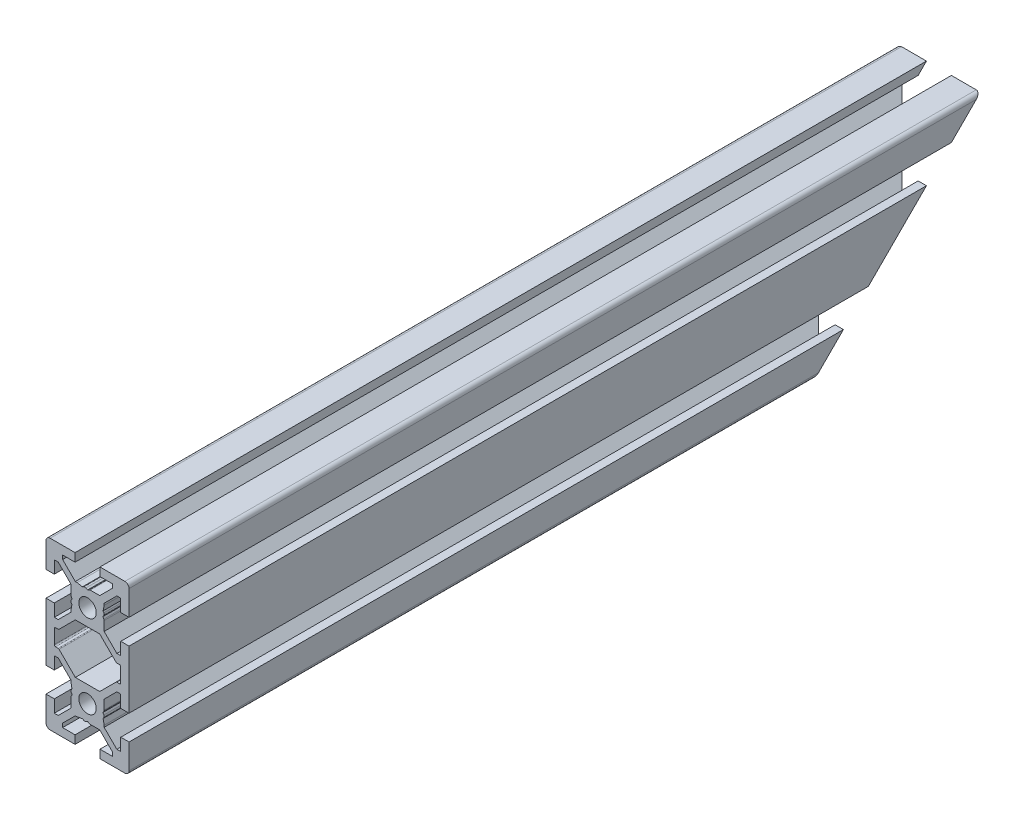
SolidWorks part; units mm, degrees
ref_plane "Front Plane" through (0, 0, 0) normal (0, 0, 1) x (1, 0, 0)
ref_plane "Top Plane" through (0, 0, 0) normal (0, 1, 0) x (1, 0, 0)
ref_plane "Right Plane" through (0, 0, 0) normal (1, 0, 0) x (0, 0, -1)
ref_plane "Plane1" through (0, 0, -600) normal (0, 0, -1) x (-1, 0, 0)
sketch "Sketch1" plane through (0, 0, -600) normal (0, 0, -1) x (-1, 0, 0)
  line L0 (8, 1.7) -> (8, -1.7)
  line L1 (7.7, -2) -> (7.0636, -2)
  line L2 (6.8515, -2.0879) -> (2.9393, -6)
  line L3 (2.9393, -6) -> (-2.9393, -6)
  line L4 (-2.9393, -6) -> (-6.8515, -2.0879)
  line L5 (-7.0636, -2) -> (-7.7, -2)
  line L6 (-8, -1.7) -> (-8, 1.7)
  line L7 (-7.7, 2) -> (-7.0636, 2)
  line L8 (-6.8515, 2.0879) -> (-2.9393, 6)
  line L9 (-2.9393, 6) -> (2.9393, 6)
  line L10 (2.9393, 6) -> (6.8515, 2.0879)
  line L11 (7.0636, 2) -> (7.7, 2)
  line L12 (10, -7) -> (10, 7)
  line L13 (10, 7) -> (8, 7)
  line L14 (8, 7) -> (8, 4)
  line L15 (8, 4) -> (7.0607, 4)
  line L16 (7.0607, 4) -> (4, 7.0607)
  line L17 (4, 7.0607) -> (4, 7.5)
  line L18 (4, 7.5) -> (3.751, 8.7811)
  line L19 (3.751, 8.7811) -> (3.933, 9.0964)
  line L20 (3.933, 9.5964) -> (3.7, 10)
  line L21 (3.7, 10) -> (3.933, 10.4036)
  line L22 (4, 10.6536) -> (4, 12.9393)
  line L23 (4, 12.9393) -> (7.0607, 16)
  line L24 (7.0607, 16) -> (8, 16)
  line L25 (8, 16) -> (8, 13)
  line L26 (8, 13) -> (10, 13)
  line L27 (10, 13) -> (10, 19)
  line L28 (9, 20) -> (3, 20)
  line L29 (3, 20) -> (3, 18)
  line L30 (3, 18) -> (6, 18)
  line L31 (6, 18) -> (6, 17.0607)
  line L32 (6, 17.0607) -> (2.9393, 14)
  line L33 (2.9393, 14) -> (2.5, 14)
  line L34 (2.5, 14) -> (1.2189, 13.751)
  line L35 (1.2189, 13.751) -> (0.9036, 13.933)
  line L36 (0.4036, 13.933) -> (0, 13.7)
  line L37 (0, 13.7) -> (-0.4036, 13.933)
  line L38 (-0.6536, 14) -> (-2.9393, 14)
  line L39 (-2.9393, 14) -> (-6, 17.0607)
  line L40 (-6, 17.0607) -> (-6, 18)
  line L41 (-6, 18) -> (-3, 18)
  line L42 (-3, 18) -> (-3, 20)
  line L43 (-3, 20) -> (-9, 20)
  line L44 (-10, 19) -> (-10, 13)
  line L45 (-10, 13) -> (-8, 13)
  line L46 (-8, 13) -> (-8, 16)
  line L47 (-8, 16) -> (-7.0607, 16)
  line L48 (-7.0607, 16) -> (-4, 12.9393)
  line L49 (-4, 12.9393) -> (-4, 12.5)
  line L50 (-4, 12.5) -> (-3.751, 11.2189)
  line L51 (-3.751, 11.2189) -> (-3.933, 10.9036)
  line L52 (-3.933, 10.4036) -> (-3.7, 10)
  line L53 (-3.7, 10) -> (-3.933, 9.5964)
  line L54 (-4, 9.3464) -> (-4, 7.0607)
  line L55 (-4, 7.0607) -> (-7.0607, 4)
  line L56 (-7.0607, 4) -> (-8, 4)
  line L57 (-8, 4) -> (-8, 7)
  line L58 (-8, 7) -> (-10, 7)
  line L59 (-10, 7) -> (-10, -7)
  line L60 (-10, -7) -> (-8, -7)
  line L61 (-8, -7) -> (-8, -4)
  line L62 (-8, -4) -> (-7.0607, -4)
  line L63 (-7.0607, -4) -> (-4, -7.0607)
  line L64 (-4, -7.0607) -> (-4, -9.3464)
  line L65 (-3.933, -9.5964) -> (-3.7, -10)
  line L66 (-3.7, -10) -> (-3.933, -10.4036)
  line L67 (-3.933, -10.9036) -> (-3.751, -11.2189)
  line L68 (-3.751, -11.2189) -> (-4, -12.5)
  line L69 (-4, -12.5) -> (-4, -12.9393)
  line L70 (-4, -12.9393) -> (-7.0607, -16)
  line L71 (-7.0607, -16) -> (-8, -16)
  line L72 (-8, -16) -> (-8, -13)
  line L73 (-8, -13) -> (-10, -13)
  line L74 (-10, -13) -> (-10, -19)
  line L75 (-9, -20) -> (-3, -20)
  line L76 (-3, -20) -> (-3, -18)
  line L77 (-3, -18) -> (-6, -18)
  line L78 (-6, -18) -> (-6, -17.0607)
  line L79 (-6, -17.0607) -> (-2.9393, -14)
  line L80 (-2.9393, -14) -> (-0.6536, -14)
  line L81 (-0.4036, -13.933) -> (0, -13.7)
  line L82 (0, -13.7) -> (0.4036, -13.933)
  line L83 (0.9036, -13.933) -> (1.2189, -13.751)
  line L84 (1.2189, -13.751) -> (2.5, -14)
  line L85 (2.5, -14) -> (2.9393, -14)
  line L86 (2.9393, -14) -> (6, -17.0607)
  line L87 (6, -17.0607) -> (6, -18)
  line L88 (6, -18) -> (3, -18)
  line L89 (3, -18) -> (3, -20)
  line L90 (3, -20) -> (9, -20)
  line L91 (10, -19) -> (10, -13)
  line L92 (10, -13) -> (8, -13)
  line L93 (8, -13) -> (8, -16)
  line L94 (8, -16) -> (7.0607, -16)
  line L95 (7.0607, -16) -> (4, -12.9393)
  line L96 (4, -12.9393) -> (4, -10.6536)
  line L97 (3.933, -10.4036) -> (3.7, -10)
  line L98 (3.7, -10) -> (3.933, -9.5964)
  line L99 (3.933, -9.0964) -> (3.751, -8.7811)
  line L100 (3.751, -8.7811) -> (4, -7.5)
  line L101 (4, -7.5) -> (4, -7.0607)
  line L102 (4, -7.0607) -> (7.0607, -4)
  line L103 (7.0607, -4) -> (8, -4)
  line L104 (8, -4) -> (8, -7)
  line L105 (8, -7) -> (10, -7)
  circle A0 centre (0, -10) radius 2.1
  circle A1 centre (0, 10) radius 2.1
  arc A2 (7.7, 2) -> (8, 1.7) centre (7.7, 1.7) cw
  arc A3 (8, -1.7) -> (7.7, -2) centre (7.7, -1.7) cw
  arc A4 (7.0636, -2) -> (6.8515, -2.0879) centre (7.0636, -2.3) ccw
  arc A5 (-6.8515, -2.0879) -> (-7.0636, -2) centre (-7.0636, -2.3) ccw
  arc A6 (-7.7, -2) -> (-8, -1.7) centre (-7.7, -1.7) cw
  arc A7 (-8, 1.7) -> (-7.7, 2) centre (-7.7, 1.7) cw
  arc A8 (-7.0636, 2) -> (-6.8515, 2.0879) centre (-7.0636, 2.3) ccw
  arc A9 (6.8515, 2.0879) -> (7.0636, 2) centre (7.0636, 2.3) ccw
  arc A10 (3.933, 9.0964) -> (3.933, 9.5964) centre (3.5, 9.3464) ccw
  arc A11 (3.933, 10.4036) -> (4, 10.6536) centre (3.5, 10.6536) ccw
  arc A12 (10, 19) -> (9, 20) centre (9, 19) ccw
  arc A13 (0.9036, 13.933) -> (0.4036, 13.933) centre (0.6536, 13.5) ccw
  arc A14 (-0.4036, 13.933) -> (-0.6536, 14) centre (-0.6536, 13.5) ccw
  arc A15 (-9, 20) -> (-10, 19) centre (-9, 19) ccw
  arc A16 (-3.933, 10.9036) -> (-3.933, 10.4036) centre (-3.5, 10.6536) ccw
  arc A17 (-3.933, 9.5964) -> (-4, 9.3464) centre (-3.5, 9.3464) ccw
  arc A18 (-4, -9.3464) -> (-3.933, -9.5964) centre (-3.5, -9.3464) ccw
  arc A19 (-3.933, -10.4036) -> (-3.933, -10.9036) centre (-3.5, -10.6536) ccw
  arc A20 (-10, -19) -> (-9, -20) centre (-9, -19) ccw
  arc A21 (-0.6536, -14) -> (-0.4036, -13.933) centre (-0.6536, -13.5) ccw
  arc A22 (0.4036, -13.933) -> (0.9036, -13.933) centre (0.6536, -13.5) ccw
  arc A23 (9, -20) -> (10, -19) centre (9, -19) ccw
  arc A24 (4, -10.6536) -> (3.933, -10.4036) centre (3.5, -10.6536) ccw
  arc A25 (3.933, -9.5964) -> (3.933, -9.0964) centre (3.5, -9.3464) ccw
  dimension "D1" = 4.2
  dimension "D3" = 0.3
  dimension "D4" = 0.3
  dimension "D5" = 0.3
  dimension "D6" = 0.3
  dimension "D7" = 0.3
  dimension "D8" = 0.3
  dimension "D9" = 0.3
  dimension "D10" = 0.5
  dimension "D11" = 0.5
  dimension "D12" = 1
  dimension "D13" = 0.5
  dimension "D14" = 0.5
  dimension "D15" = 1
  dimension "D16" = 0.5
  dimension "D17" = 0.5
  dimension "D18" = 0.5
  dimension "D19" = 0.5
  dimension "D20" = 0.4036
  dimension "D21" = 0.5
  dimension "D22" = 0.5
  dimension "D23" = 1
  dimension "D24" = 0.5
  dimension "D25" = 0.5
  dimension "D26" = 0.4036
  dimension "D27" = 0.6536
  dimension "D28" = 0.6536
  dimension "D29" = 0.9036
  dimension "D30" = 0.9036
  dimension "D31" = 1.2189
  dimension "D32" = 1.2189
  dimension "D33" = 2.5
  dimension "D34" = 2.5
  dimension "D35" = 2.9393
  dimension "D36" = 2.9393
  dimension "D37" = 3
  dimension "D38" = 3.5
  dimension "D39" = 6
  dimension "D40" = 6.8515
  dimension "D41" = 3.7
  dimension "D42" = 3.7
  dimension "D43" = 3.751
  dimension "D44" = 3.751
  dimension "D45" = 3.933
  dimension "D46" = 3.933
  dimension "D47" = 6.8515
  dimension "D48" = 7.0607
  dimension "D49" = 7.0607
  dimension "D50" = 7.0636
  dimension "D51" = 7.0636
  dimension "D52" = 8
  dimension "D53" = 10
  dimension "D54" = 3
  dimension "D55" = 4
  dimension "D56" = 6
  dimension "D57" = 6.8515
  dimension "D58" = 6.8515
  dimension "D59" = 7.0607
  dimension "D60" = 7.0607
  dimension "D61" = 0.4036
  dimension "D62" = 0.4036
  dimension "D63" = 0.6536
  dimension "D64" = 0.6536
  dimension "D65" = 2.9393
  dimension "D66" = 2.9393
  dimension "D67" = 8
  dimension "D68" = 2
  dimension "D69" = 3.5
  dimension "D70" = 3.5
  dimension "D71" = 3.7
  dimension "D72" = 3.7
  dimension "D73" = 3.751
  dimension "D74" = 3.751
  dimension "D75" = 3.933
  dimension "D76" = 3.933
  dimension "D77" = 4
  dimension "D78" = 6
  dimension "D79" = 7
  dimension "D80" = 7.0607
  dimension "D81" = 7.0607
  dimension "D82" = 7.5
  dimension "D83" = 8.7811
  dimension "D84" = 9.0964
  dimension "D85" = 9.3464
  dimension "D86" = 9.3464
  dimension "D87" = 9.5964
  dimension "D88" = 9.5964
  dimension "D89" = 10.4036
  dimension "D90" = 12.5
  dimension "D91" = 13
  dimension "D92" = 13.5
  dimension "D93" = 13.5
  dimension "D94" = 18
  dimension "D95" = 20
  dimension "D96" = 2
  dimension "D97" = 4
  dimension "D98" = 6
  dimension "D99" = 7
  dimension "D100" = 7.0607
  dimension "D101" = 7.0607
  dimension "D102" = 7.5
  dimension "D103" = 8.7811
  dimension "D104" = 9.0964
  dimension "D105" = 9.3464
  dimension "D106" = 9.3464
  dimension "D107" = 9.5964
  dimension "D108" = 9.5964
  dimension "D109" = 10.4036
  dimension "D110" = 12.5
  dimension "D111" = 13
  dimension "D112" = 18
extrude "Boss-Extrude1" add sketch "Sketch1" against normal blind 205.03
sketch "Sketch2" plane through (-10, 0, 0) normal (-1, 0, 0) x (0, 0, 1)
  line L0 (-600, 20) -> (-560, -20)
  line L1 (-394.97, -20) -> (-600, -20) construction
  line L2 (-560, -20) -> (-600, -20)
  line L3 (-600, -20) -> (-600, 20)
  dimension "D1" = 45
extrude "Cut-Extrude1" cut sketch "Sketch2" against normal through all
